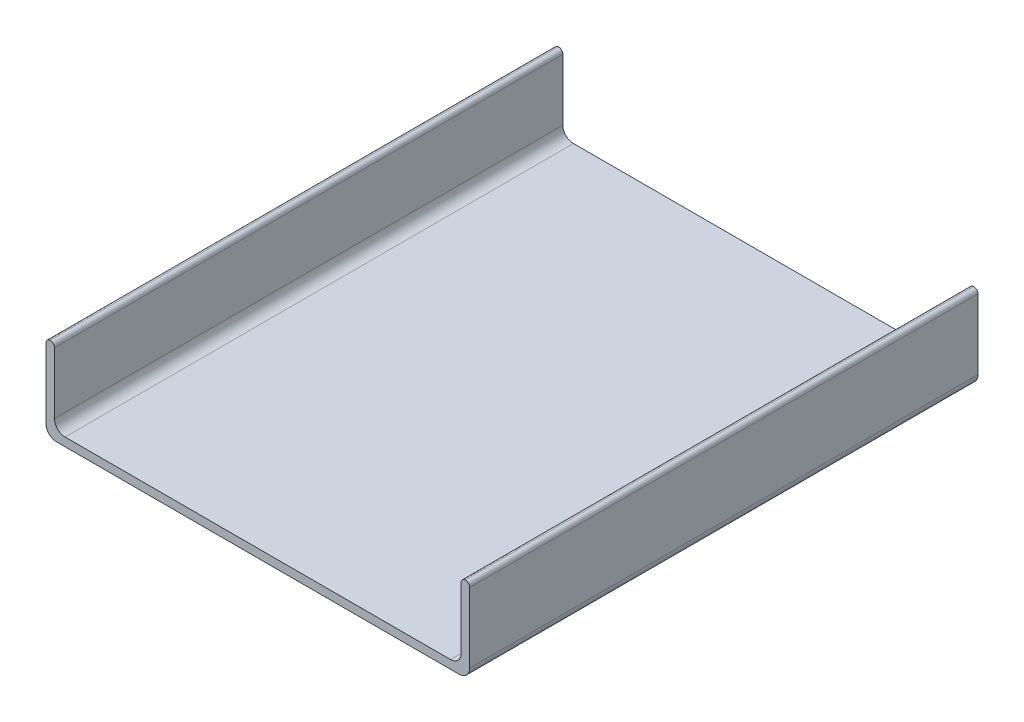
SolidWorks part; units mm, degrees
ref_plane "Front Plane" through (0, 0, 0) normal (0, 0, 1) x (1, 0, 0)
ref_plane "Top Plane" through (0, 0, 0) normal (0, 1, 0) x (1, 0, 0)
ref_plane "Right Plane" through (0, 0, 0) normal (1, 0, 0) x (0, 0, -1)
sketch "Sketch5" plane through (0, 0, 0) normal (0, 0, 1) x (1, 0, 0)
  line L1 (-2.6896, 0.9558) -> (88.3104, 0.9558)
  line L2 (-7.1896, 2.9558) -> (-7.1896, 1.4558)
  line L3 (-4.6896, -1.0442) -> (90.3104, -1.0442)
  line L4 (92.8104, 2.9558) -> (92.8104, 1.4558)
  line L6 (-7.1896, 2.9558) -> (-7.1896, 18.9558)
  line L7 (-7.1896, 18.9558) -> (-5.1896, 18.9558)
  line L8 (-5.1896, 3.4558) -> (-5.1896, 18.9558)
  line L10 (92.8104, 2.9558) -> (92.8104, 18.9558)
  line L11 (92.8104, 18.9558) -> (90.8104, 18.9558)
  line L12 (90.8104, 3.4558) -> (90.8104, 18.9558)
  arc A0 (88.3104, 0.9558) -> (90.8104, 3.4558) centre (88.3104, 3.4558) ccw
  arc A1 (-2.6896, 0.9558) -> (-5.1896, 3.4558) centre (-2.6896, 3.4558) cw
  arc A2 (90.3104, -1.0442) -> (92.8104, 1.4558) centre (90.3104, 1.4558) ccw
  arc A3 (-7.1896, 1.4558) -> (-4.6896, -1.0442) centre (-4.6896, 1.4558) ccw
  point P17 (92.8104, -1.0442)
  point P20 (-7.1896, -1.0442)
  dimension "D7" = 2.5
  dimension "D1" = 4
  dimension "D2" = 100
  dimension "D3" = 20
  dimension "D4" = 20
  dimension "D5" = 2
  dimension "D6" = 2
  dimension "D8" = 2
extrude "Boss-Extrude3" add sketch "Sketch5" along normal blind 120
fillet "Fillet4" radius 1 4 edges at (92.8104, 18.9558, 60) (90.8104, 18.9558, 60) (-7.1896, 18.9558, 60) (-5.1896, 18.9558, 60)
